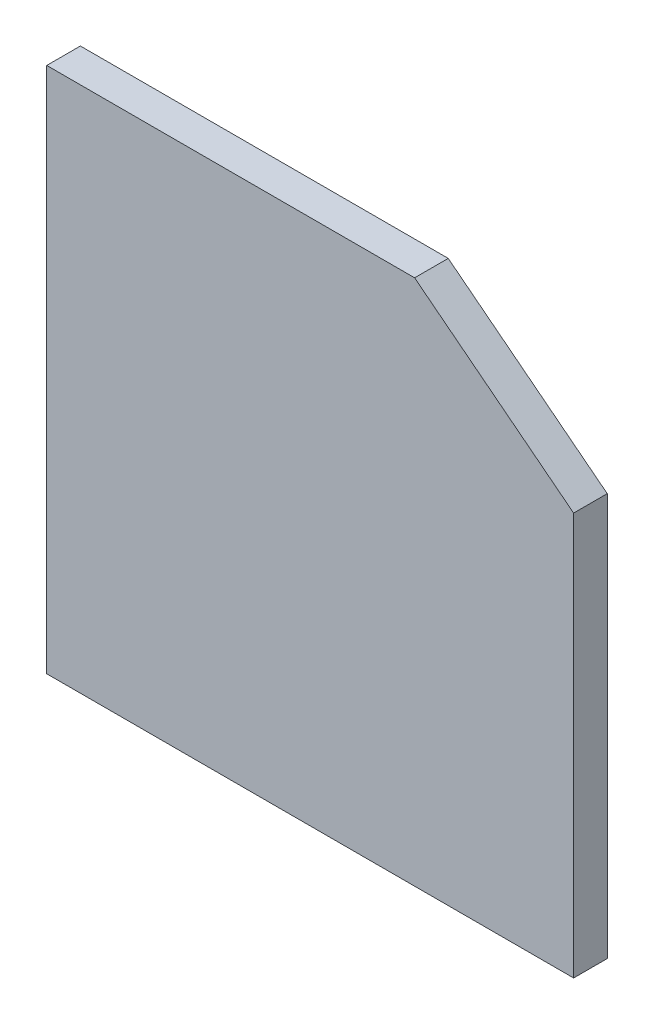
SolidWorks part; units mm, degrees
ref_plane "Front Plane" through (0, 0, 0) normal (0, 0, 1) x (1, 0, 0)
ref_plane "Top Plane" through (0, 0, 0) normal (0, 1, 0) x (1, 0, 0)
ref_plane "Right Plane" through (0, 0, 0) normal (1, 0, 0) x (0, 0, -1)
sketch "Sketch1" plane through (0, 0, 0) normal (0, 0, 1) x (1, 0, 0)
  line L0 (32.8158, 47) -> (47, 35.9181)
  line L1 (0, 0) -> (47, 0)
  line L2 (0, 0) -> (0, 47)
  line L3 (0, 47) -> (47, 47)
  line L4 (47, 0) -> (47, 47)
  dimension "D1" = 47
  dimension "D2" = 47
  dimension "D3" = 38
  dimension "D4" = 18
extrude "Boss-Extrude1" add sketch "Sketch1" along normal blind 3 contours L1 L4 L0 L3 L2 region at (22.8075, 22.7693, 0)
